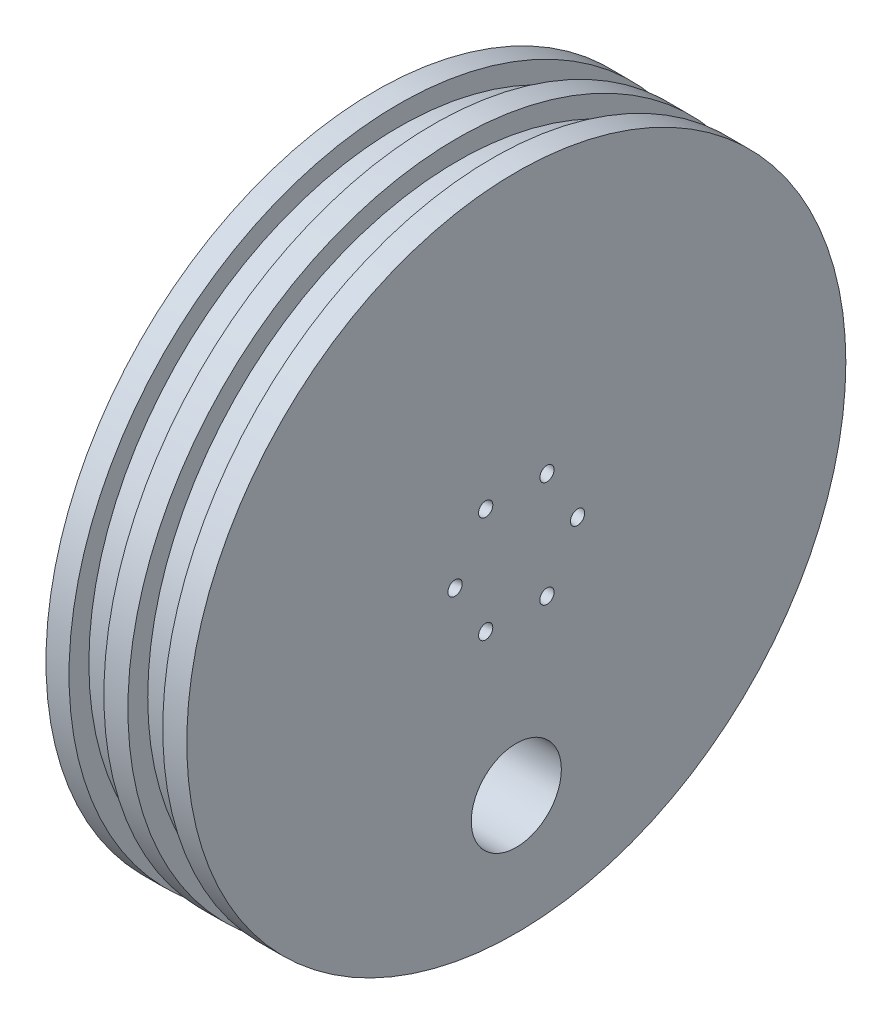
SolidWorks part; units mm, degrees
note: '?' marks a value the reader was unsure of.
material "6061 Alloy"
ref_plane "Front Plane" through (0, 0, 0) normal (0, 0, 1) x (1, 0, 0)
ref_plane "Top Plane" through (0, 0, 0) normal (0, 1, 0) x (1, 0, 0)
ref_plane "Right Plane" through (0, 0, 0) normal (1, 0, 0) x (0, 0, -1)
ref_axis "Axis1" through (17.7799, 0, 0) along (-1, 0, 0)
sketch "Sketch1" plane through (0, 0, 0) normal (0, 0, 1) x (1, 0, 0)
  line L0 (0, -34.8361) -> (0, 34.8361)
  line L1 (0, 34.8361) -> (-2.54, 34.8361)
  line L2 (-2.54, 34.8361) -> (-2.54, 32.7406)
  line L3 (-2.54, 32.7406) -> (-6.223, 32.7406)
  line L4 (-6.223, 32.7406) -> (-6.223, 34.8361)
  line L5 (-6.223, 34.8361) -> (-8.763, 34.8361)
  line L6 (-8.763, 34.8361) -> (-8.763, 32.7406)
  line L7 (-8.763, 32.7406) -> (-12.446, 32.7406)
  line L8 (-12.446, 32.7406) -> (-12.446, 34.8361)
  line L9 (-12.446, 34.8361) -> (-14.885, 34.8361)
  line L12 (-18.06, 29.1592) -> (-18.06, 4.7625)
  line L13 (-12.599, 0) -> (0, 0)
  line L17 (-12.446, -32.7406) -> (-12.446, -34.8361)
  line L18 (-8.763, -32.7406) -> (-12.446, -32.7406)
  line L19 (-8.763, -34.8361) -> (-8.763, -32.7406)
  line L20 (-6.223, -34.8361) -> (-8.763, -34.8361)
  line L21 (-6.223, -32.7406) -> (-6.223, -34.8361)
  line L22 (-2.54, -32.7406) -> (-6.223, -32.7406)
  line L23 (-2.54, -34.8361) -> (-2.54, -32.7406)
  line L24 (0, -34.8361) -> (-2.54, -34.8361)
  line L25 (-18.06, 4.7625) -> (-12.599, 4.7625)
  line L26 (-12.599, 4.7625) -> (-12.599, 0)
  line L27 (-12.599, 0) -> (-12.599, -4.7625)
  line L28 (-12.599, -4.7625) -> (-18.06, -4.7625)
  line L29 (-18.06, -4.7625) -> (-18.06, -29.1592)
  line L30 (-18.06, 4.7625) -> (-18.06, -4.7625) construction
  line L31 (-14.885, 34.8361) -> (-14.885, 29.1592)
  line L32 (-14.885, 29.1592) -> (-18.06, 29.1592)
  dimension "D1" = 69.6722
  dimension "D2" = 3.683
  dimension "D3" = 65.4812
  dimension "D4" = 2.54
  dimension "D5" = 58.3184
  dimension "D7" = 18.06
  dimension "D8" = 2.54
  dimension "D9" = 9.525
  dimension "D10" = 5.461
  dimension "D11" = 3.175
revolve "Revolve1" add sketch "Sketch1" angle 360 about axis through (17.7799, 0, 0) along (-1, 0, 0)
sketch "Sketch22" plane through (-18.06, 0, 0) normal (-1, 0, 0) x (0, 0, 1)
  line L0 (0, 0) -> (0, 22.225) construction
  circle A0 centre (0, 0) radius 22.225 construction
  point P5 (0, 22.225)
  dimension "D1" = 44.45
hole_wizard "#20 (0.161) Diameter Hole1" positions "Sketch23" profile "Sketch24" hole size "#20" standard "ANSI Inch"
sketch "Sketch23" plane through (-18.06, 0, 0) normal (-1, 0, 0) x (0, 0, 1)
  point P0 (0, 22.225)
sketch "Sketch24" plane through (-18.06, 22.225, 0) normal (0, 1, 0) x (0, 0, 1)
  line L0 (0, 0) -> (0, 10.8806)
  line L1 (0, 10.8806) -> (2.0447, 9.652)
  line L2 (2.0447, 9.652) -> (2.0447, 0)
  line L5 (2.0447, 0) -> (0, 0)
  line L10 (0, 10.8806) -> (-2.0447, 9.652) construction
  line L11 (0, -6.35) -> (0, 107.95) construction
  dimension "Hole Dia." = 4.0894
  dimension "Hole Depth" = 9.652
  dimension "Drill Angle" = 118
pattern_circular "CirPattern2" count 3 over 360 about axis through (0, 0, 0) along (1, 0, 0) of "#20 (0.161) Diameter Hole1"
ref_plane "Top of Part" through (0, 0, 0) normal (1, 0, 0) x (0, 0, -1)
ref_axis "Axis2" through (0, -42.1217, 0) along (0, 1, 0)?
ref_axis "Axis3" through (-26.67, 0, 0) along (1, 0, 0)?
ref_plane "Plane3" through (0, 0, 0) normal (0, -0.5, 0.866) x (1, 0, 0)
ref_axis "Axis4" through (0, -1.4216, -0.8207) along (0, 0.866, 0.5)?
ref_plane "Plane7" through (0, 0, 0) normal (0.9877, -0.0782, 0.1355) x (0, 0.866, 0.5)
sketch "Sketch7" plane through (0, 0, 0) normal (1, 0, 0) x (0, 0, -1)
  line L0 (0, 0) -> (0, 6.477) construction
  line L1 (0, 0) -> (3.2385, 5.6092) construction
  line L2 (0, 0) -> (6.477, 0) construction
  line L3 (0, 0) -> (3.2385, -5.6092) construction
  line L4 (0, 0) -> (-3.2385, -5.6092) construction
  line L5 (0, 0) -> (-6.477, 0) construction
  line L7 (0, 0) -> (-3.2385, 5.6092) construction
  circle A0 centre (0, 0) radius 6.477 construction
  point P12 (0, 0)
  point P13 (0, 0)
  dimension "D2" = 12.954
  dimension "D3" = 30
  dimension "D1" = 6
sketch "Sketch17" plane through (0, 0, 0) normal (0.9877, -0.0782, 0.1355) x (0, 0.866, 0.5)
  point P0 (-3.2385, -5.5402)
hole_wizard "Ø1.5 (1.5) Diameter Hole4" positions "Sketch18" profile "Sketch19" hole size "Ø1.5" standard "ANSI Metric"
sketch "Sketch18" plane through (0, 0, 0) normal (0.9877, -0.0782, 0.1355) x (0, 0.866, 0.5)
  point P0 (-3.2385, -5.5402)
sketch "Sketch19" plane through (0.8667, -0.0686, -6.3581) normal (-0.041, 0.7065, 0.7065) x (0.151, 0.7034, -0.6946)
  line L0 (0, 0) -> (0, 24.5196)
  line L1 (0, 24.5196) -> (0.75, 24.069)
  line L2 (0.75, 24.069) -> (0.75, 0)
  line L5 (0.75, 0) -> (0, 0)
  line L10 (0, 24.5196) -> (-0.75, 24.069) construction
  line L11 (0, -6.35) -> (0, 107.95) construction
  dimension "Hole Dia." = 1.5
  dimension "Hole Depth" = 24.069
  dimension "Drill Angle" = 118
ref_plane "Plane8" through (0, 0, 0) normal (1, 0, 0) x (0, 0, -1)
pattern_circular "CirPattern1" count 6 over 360 about axis through (-26.67, 0, 0) along (1, 0, 0) of "Ø1.5 (1.5) Diameter Hole4"
ref_axis "Axis7" through (-9.5533, 6.3658, 4.5489) along (0.9877, -0.0782, -0.1355)?
ref_axis "Axis8" through (-9.622, 7.1332, -3.2385) along (0.9877, -0.1564, 0)?
ref_axis "Axis9" through (-10.3183, 0.8171, -7.8923) along (0.9877, -0.0782, 0.1355)?
ref_axis "Axis10" through (-9.0092, -6.3227, -4.4742) along (0.9877, 0.0782, 0.1355)?
ref_axis "Axis11" through (-10.5844, -7.2856, 3.2385) along (0.9877, 0.1564, 0)?
ref_axis "Axis12" through (-9.8881, -0.7831, 7.8333) along (0.9877, 0.0782, -0.1355)?
sketch "Sketch20" plane through (0, 0, 0) normal (1, 0, 0) x (0, 0, -1)
  ellipse E0 centre (-6.477, 0) end of major axis (-5.8194, 0.3797) minor radius 0.75 construction
  point P0 (-7.234, -0.0132)
sketch "Sketch21" plane through (-18.06, 0, 0) normal (-1, 0, 0) x (0, 0, 1)
  ellipse E0 centre (8.9542, -1.4302) end of major axis (8.2966, -1.0505) minor radius 0.75 construction
  point P0 (9.7079, -1.3677)
hole_wizard "Ø1.5mm Dowel Hole1" [suppressed] positions "Sketch36" profile "Sketch37" hole size "Ø1.5" standard "ANSI Metric"
sketch "Sketch36" [suppressed] plane through (0, 0, 0) normal (1, 0, 0) x (0, 0, -1)
  point P0 (0, 0)
sketch "Sketch37" [suppressed] plane through (0, 0, 0) normal (0, 1, 0) x (0, 0, -1)
  line L0 (0, 0) -> (0, 25.4)
  line L1 (0, 25.4) -> (0.75, 25.4)
  line L2 (0.75, 25.4) -> (0.75, 0)
  line L5 (0.75, 0) -> (0, 0)
  line L11 (0, -6.35) -> (0, 107.95) construction
  dimension "Thru Hole Dia." = 1.5
  dimension "Thru Hole Depth" = 25.4
hole_wizard "#8-32 Tapped Hole1" positions "Sketch40" profile "Sketch41" tap size "#8-32" standard "ANSI Inch"
sketch "Sketch40" plane through (-12.599, 0, 0) normal (-1, 0, 0) x (0, 0, 1)
  point P0 (0, 0)
sketch "Sketch41" plane through (-12.599, 0, 0) normal (0, 1, 0) x (0, 0, 1)
  line L0 (0, 0) -> (0, 7.3878)
  line L1 (0, 7.3878) -> (1.7272, 6.35)
  line L2 (1.7272, 6.35) -> (1.7272, 0)
  line L5 (1.7272, 0) -> (0, 0)
  line L10 (0, 7.3878) -> (-1.7272, 6.35) construction
  line L11 (0, -6.35) -> (0, 107.95) construction
  dimension "Tap Drill Dia." = 3.4544
  dimension "Tap Drill Depth" = 6.35
  dimension "Drill Angle" = 118
cosmetic thread "Hole Thread3" parameters "D1"=6.35, "D2"=4.1656
sketch "Sketch43" plane through (-18.06, 0, 0) normal (-1, 0, 0) x (0, 0, 1)
  line L0 (0, 0) -> (0, 22.225) construction
  line L1 (0, 22.225) -> (19.2474, -11.1125) construction
  line L2 (19.2474, -11.1125) -> (0, 0) construction
  line L3 (0, 0) -> (19.6324, 11.3347) construction
  circle A0 centre (0, 0) radius 22.6695 construction
  point P8 (9.6237, 5.5562)
  dimension "D1" = 45.339
hole_wizard "#50 (0.07) Diameter Hole1" positions "Sketch44" profile "Sketch45" hole size "#50" standard "ANSI Inch"
sketch "Sketch44" plane through (-18.06, 0, 0) normal (-1, 0, 0) x (0, 0, 1)
  point P0 (19.6324, 11.3347)
sketch "Sketch45" plane through (-18.06, 11.3347, 19.6324) normal (0, 1, 0) x (0, 0, 1)
  line L0 (0, 0) -> (0, 12.4722)
  line L1 (0, 12.4722) -> (0.889, 11.938)
  line L2 (0.889, 11.938) -> (0.889, 0)
  line L5 (0.889, 0) -> (0, 0)
  line L10 (0, 12.4722) -> (-0.889, 11.938) construction
  line L11 (0, -6.35) -> (0, 107.95) construction
  dimension "Hole Dia." = 1.778
  dimension "Hole Depth" = 11.938
  dimension "Drill Angle" = 118
sketch "Sketch46" plane through (0, 0, 0) normal (1, 0, 0) x (0, 0, -1)
  line L0 (0, 0) -> (-19.2474, -11.1125) construction
  line L1 (-19.2474, -11.1125) -> (19.2474, -11.1125) construction
  line L2 (19.2474, -11.1125) -> (0, 0) construction
  line L3 (0, 0) -> (0, -22.225) construction
  circle A0 centre (0, 0) radius 22.225 construction
  point P3 (0, -11.1125)
  dimension "D1" = 44.45
hole_wizard "Q (0.332) Diameter Hole1" positions "Sketch47" profile "Sketch48" hole size "Q" standard "ANSI Inch" end condition through all
sketch "Sketch47" plane through (-18.06, 0, 0) normal (-1, 0, 0) x (0, 0, 1)
  point P0 (0, -22.225)
sketch "Sketch48" plane through (-18.06, -22.225, 0) normal (0, 1, 0) x (0, 0, 1)
  line L0 (0, 0) -> (0, 18.06)
  line L1 (0, 18.06) -> (4.2164, 18.06)
  line L2 (4.2164, 18.06) -> (4.2164, 0)
  line L5 (4.2164, 0) -> (0, 0)
  line L11 (0, -6.35) -> (0, 107.95) construction
  dimension "Thru Hole Dia." = 8.4328
  dimension "Thru Hole Depth" = 18.06
hole_wizard "3/8 (0.375) Diameter Hole1" positions "Sketch49" profile "Sketch51" hole size "3/8" standard "ANSI Inch"
sketch "Sketch49" plane through (0, 0, 0) normal (1, 0, 0) x (0, 0, -1)
  point P0 (0, -22.225)
sketch "Sketch51" plane through (0, -22.225, 0) normal (0, 1, 0) x (0, 0, -1)
  line L0 (0, 0) -> (0, 12.0056)
  line L1 (0, 12.0056) -> (4.7625, 9.144)
  line L2 (4.7625, 9.144) -> (4.7625, 0)
  line L5 (4.7625, 0) -> (0, 0)
  line L10 (0, 12.0056) -> (-4.7625, 9.144) construction
  line L11 (0, -6.35) -> (0, 107.95) construction
  dimension "Hole Dia." = 9.525
  dimension "Hole Depth" = 9.144
  dimension "Drill Angle" = 118
